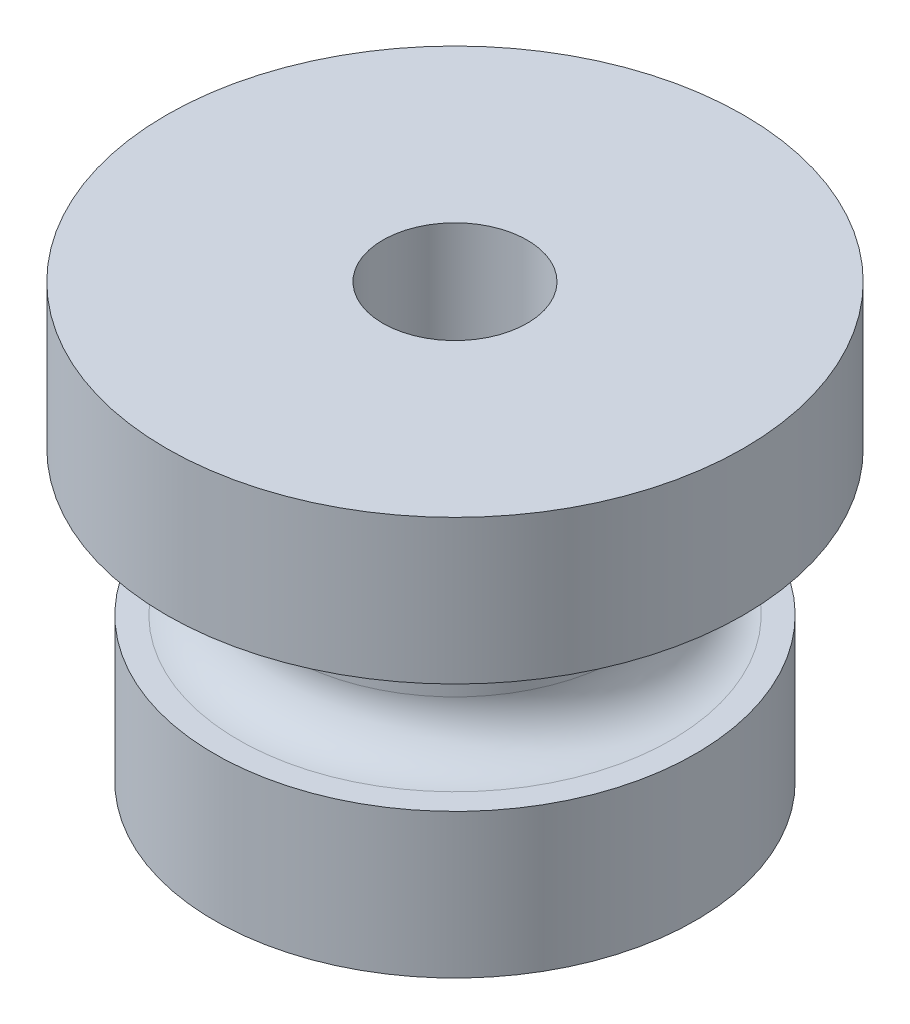
SolidWorks part; units mm, degrees
ref_plane "Front Plane" through (0, 0, 0) normal (0, 0, 1) x (1, 0, 0)
ref_plane "Top Plane" through (0, 0, 0) normal (0, 1, 0) x (1, 0, 0)
ref_plane "Right Plane" through (0, 0, 0) normal (1, 0, 0) x (0, 0, -1)
sketch "Sketch1" plane through (0, 0, 0) normal (0, 1, 0) x (1, 0, 0)
  circle A0 centre (0, 0) radius 1.5
  circle A1 centre (0, 0) radius 3.5
  dimension "D1" = 2
extrude "Boss-Extrude1" add sketch "Sketch1" along normal blind 9 contours A0 | A1 region at (0, 0, 0)
sketch "Sketch2" plane through (0, 9, 0) normal (0, 1, 0) x (1, 0, 0)
  circle A0 centre (0, 0) radius 1.5
  circle A1 centre (0, 0) radius 6
extrude "Boss-Extrude2" add sketch "Sketch2" against normal blind 3 contours A1 | A0
sketch "Sketch3" plane through (0, 0, 0) normal (0, -1, 0) x (1, 0, 0)
  circle A0 centre (0, 0) radius 1.5
  circle A1 centre (0, 0) radius 5
extrude "Boss-Extrude3" add sketch "Sketch3" against normal blind 3 contours A1 | A0
fillet "Fillet2" radius 1 2 edges at (0, 3, -3.5) (0, 6, 3.5)
